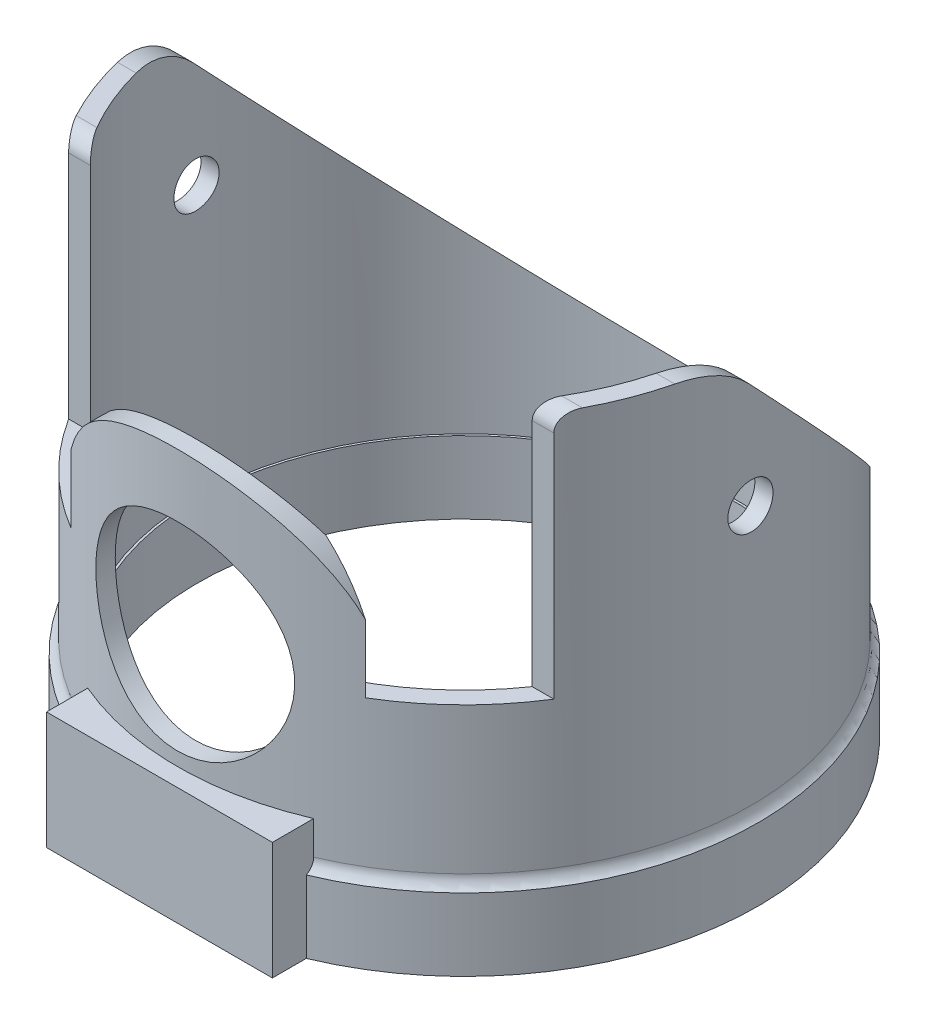
SolidWorks part; units mm, degrees
ref_plane "Спереди" through (0, 0, 0) normal (0, 0, 1) x (1, 0, 0)
ref_plane "Сверху" through (0, 0, 0) normal (0, 1, 0) x (1, 0, 0)
ref_plane "Справа" through (0, 0, 0) normal (1, 0, 0) x (0, 0, -1)
sketch "Эскиз1" plane through (0, 0, 0) normal (0, 1, 0) x (1, 0, 0)
  circle A0 centre (0, 0) radius 32.5
  circle A1 centre (0, 0) radius 29.5
  dimension "D1" = 65
  dimension "D2" = 59
extrude "lower part" add sketch "Эскиз1" along normal blind 8
sketch "Эскиз2" plane through (0, 0, 0) normal (0, -1, 0) x (1, 0, 0)
  circle A0 centre (0, 0) radius 31.5
  circle A1 centre (0, 0) radius 30
  dimension "D1" = 63
  dimension "D2" = 60
extrude "slot" cut sketch "Эскиз2" against normal blind 3
sketch "Эскиз3" plane through (0, 8, 0) normal (0, 1, 0) x (1, 0, 0)
  circle A0 centre (0, 0) radius 31.75
  circle A1 centre (0, 0) radius 29.75
  dimension "D1" = 63.5
  dimension "D2" = 59.5
extrude "higher part" add sketch "Эскиз3" along normal blind 45
sketch "Эскиз4" plane through (0, 0, 0) normal (1, 0, 0) x (0, 0, -1)
  line L0 (31.75, 53) -> (31.75, 16)
  line L1 (31.75, 8) -> (31.75, 53) construction
  line L2 (31.75, 16) -> (-3.25, 53)
  line L3 (29.75, 53) -> (-29.75, 53) construction
  line L4 (-3.25, 53) -> (31.75, 53)
  dimension "D1" = 35
  dimension "D2" = 37
extrude "triangle" cut sketch "Эскиз4" against normal through all and the other way through all
ref_plane "tube start" through (0, 0, 12) normal (0, 0, 1) x (1, 0, 0)
sketch "Эскиз7" plane through (0, 0, 0) normal (1, 0, 0) x (0, 0, -1)
  line L0 (-3.25, 53) -> (-31.75, 53) construction
  line L1 (-16.95, 53) -> (-27.25, 53)
  line L2 (-16.95, 53) -> (-16.95, 25.5)
  line L3 (-16.95, 25.5) -> (-27.25, 25.5)
  line L4 (-27.25, 53) -> (-27.25, 25.5)
  line L5 (-32.5, 0) -> (32.5, 0) construction
  dimension "D1" = 10.3
  dimension "D2" = 25.5
  dimension "D3" = 4.5
extrude "key slot" cut sketch "Эскиз7" against normal up to next and the other way up to next
sketch "Эскиз5" plane through (0, 0, 0) normal (0, 0, 1) x (1, 0, 0)
  line L0 (-32.5, 0) -> (32.5, 0) construction
  circle A0 centre (0, 25.5) radius 11
  dimension "D2" = 22
  dimension "D1" = 25.5
extrude "hole" cut sketch "Эскиз5" along normal through all
sketch "Эскиз9" plane through (0, 0, 0) normal (1, 0, 0) x (0, 0, -1)
  circle A0 centre (0, 38) radius 2.5
  dimension "D1" = 5
  dimension "D2" = 38
extrude "small hole" cut sketch "Эскиз9" against normal through all and the other way through all
sketch "Эскиз11" plane through (0, 0, 0) normal (0, 1, 0) x (1, 0, 0)
  line L0 (-12.5, -29.1858) -> (12.5, -29.1858) construction
  line L1 (12.5, -29.1858) -> (12.5, -33.75)
  line L2 (12.5, -33.75) -> (-12.5, -33.75)
  line L3 (-12.5, -33.75) -> (-12.5, -29.1858)
  line L4 (0, 0) -> (0, -31.75) construction
  circle A0 centre (0, 0) radius 31.75 construction
  arc A1 (-16.2942, -27.25) -> (16.2942, -27.25) centre (0, 0) ccw construction
  arc A2 (-12.5, -29.1858) -> (12.5, -29.1858) centre (0, 0) ccw
  dimension "D1" = 25
  dimension "D2" = 2
extrude "support" add sketch "Эскиз11" along normal blind 13
fillet "Скругление1" radius 1.5 1 edges at (0, 8, -31.75)
fillet "Скругление2" radius 10 2 edges at (-30.5776, 53, 3.25) (30.5776, 53, 3.25)
fillet "Скругление3" radius 2 2 edges at (-25.6481, 53, 16.95) (25.6481, 53, 16.95)
sketch "Эскиз12" plane through (0, 0, 0) normal (0, 0, 1) x (1, 0, 0)
  line L0 (16.2942, 25.5) -> (16.2942, 53) construction
  line L1 (-16.2942, 53) -> (16.2942, 53)
  line L4 (16.2942, 53) -> (16.2942, 33)
  line L5 (-16.2942, 53) -> (-16.2942, 33)
  line L6 (-16.2942, 25.5) -> (-16.2942, 53) construction
  arc A0 (-16.2942, 33) -> (16.2942, 33) centre (0, 25.5) cw
  circle A1 centre (0, 25.5) radius 11 construction
  dimension "D1" = 20
extrude "Вытянуть1" cut sketch "Эскиз12" along normal through all
